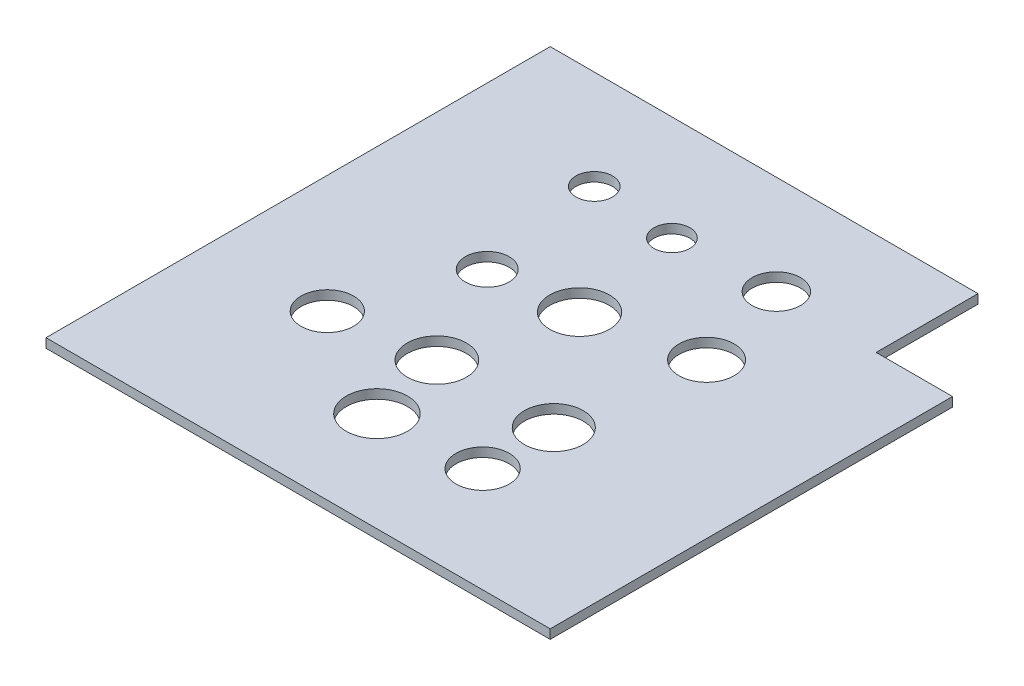
SolidWorks part; units mm, degrees
ref_plane "前视基准面" through (0, 0, 0) normal (0, 0, 1) x (1, 0, 0)
ref_plane "上视基准面" through (0, 0, 0) normal (0, 1, 0) x (1, 0, 0)
ref_plane "右视基准面" through (0, 0, 0) normal (1, 0, 0) x (0, 0, -1)
sketch "草图1" plane through (0, 0, 0) normal (0, 1, 0) x (1, 0, 0)
  line L1 (0, 0) -> (99, 0)
  line L2 (0, 0) -> (0, 99)
  line L3 (0, 99) -> (99, 99)
  line L4 (99, 0) -> (99, 99)
  dimension "D1" = 99
  dimension "D2" = 99
extrude "凸台-拉伸1" add sketch "草图1" along normal blind 1.8
sketch "草图2" plane through (0, 1.8, 0) normal (0, 1, 0) x (1, 0, 0)
  circle A0 centre (28.0997, 79.5501) radius 3.5881
  circle A1 centre (44.5023, 78.3968) radius 3.5257
  circle A2 centre (63.8523, 79.5501) radius 4.7552
  circle A3 centre (31.6878, 54.9462) radius 4.3058
  circle A4 centre (48.0281, 56.7402) radius 5.8542
  circle A5 centre (68.6075, 61.0971) radius 5.4162
  circle A6 centre (23.1021, 32.1363) radius 5.1593
  circle A7 centre (42.1738, 34.5711) radius 5.818
  circle A8 centre (65.1337, 34.5711) radius 5.7748
  circle A9 centre (45.3994, 19.5781) radius 6.0064
  circle A10 centre (65.1337, 20.6032) radius 5.2273
extrude "切除-拉伸1" cut sketch "草图2" against normal through all
sketch "草图3" plane through (0, 1.8, 0) normal (0, 1, 0) x (1, 0, 0)
  line L1 (99, 99) -> (84, 99)
  line L2 (99, 99) -> (99, 79)
  line L3 (99, 79) -> (84, 79)
  line L4 (84, 99) -> (84, 79)
  dimension "D1" = 15
  dimension "D2" = 20
extrude "切除-拉伸2" cut sketch "草图3" against normal through all
